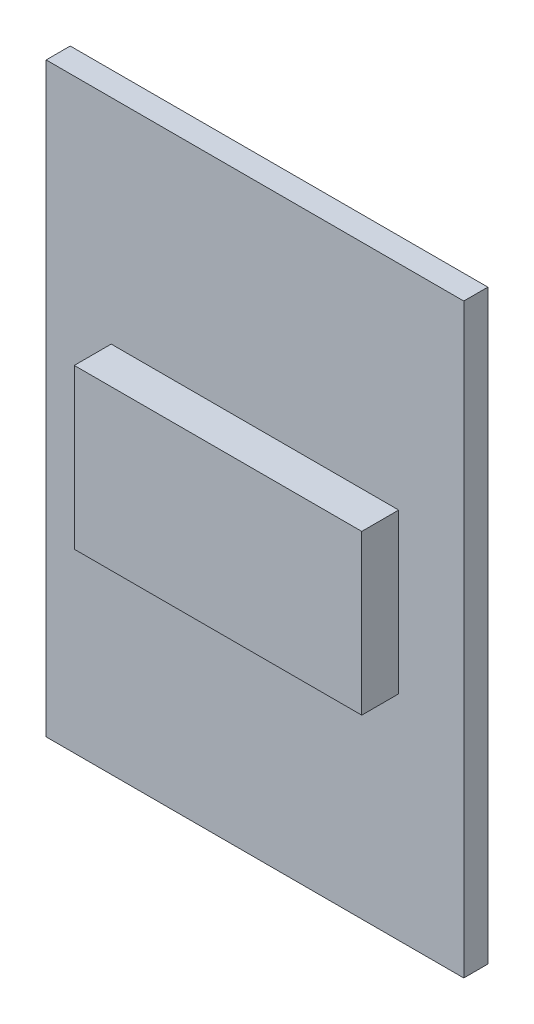
SolidWorks part; units mm, degrees
ref_plane "Alzado" through (0, 0, 0) normal (0, 0, 1) x (1, 0, 0)
ref_plane "Planta" through (0, 0, 0) normal (0, 1, 0) x (1, 0, 0)
ref_plane "Vista lateral" through (0, 0, 0) normal (1, 0, 0) x (0, 0, -1)
sketch "Croquis1" plane through (0, 0, 0) normal (0, 0, 1) x (1, 0, 0)
  line L1 (13, -18.25) -> (-13, -18.25)
  line L2 (13, -18.25) -> (13, 18.25)
  line L3 (13, 18.25) -> (-13, 18.25)
  line L4 (-13, -18.25) -> (-13, 18.25)
  line L5 (13, -18.25) -> (-13, 18.25) construction
  line L6 (13, 18.25) -> (-13, -18.25) construction
  point P0 (0, 0)
  dimension "D1" = 36.5
  dimension "D2" = 26
extrude "Saliente-Extruir1" add sketch "Croquis1" along normal blind 1.5
sketch "Croquis2" plane through (0, 0, 1.5) normal (0, 0, 1) x (1, 0, 0)
  line L1 (8.9488, -4.9547) -> (-8.9488, -4.9547)
  line L2 (8.9488, -4.9547) -> (8.9488, 4.9547)
  line L3 (8.9488, 4.9547) -> (-8.9488, 4.9547)
  line L4 (-8.9488, -4.9547) -> (-8.9488, 4.9547)
  line L5 (8.9488, -4.9547) -> (-8.9488, 4.9547) construction
  line L6 (8.9488, 4.9547) -> (-8.9488, -4.9547) construction
  point P0 (0, 0)
extrude "Saliente-Extruir2" add sketch "Croquis2" along normal blind 2.3
